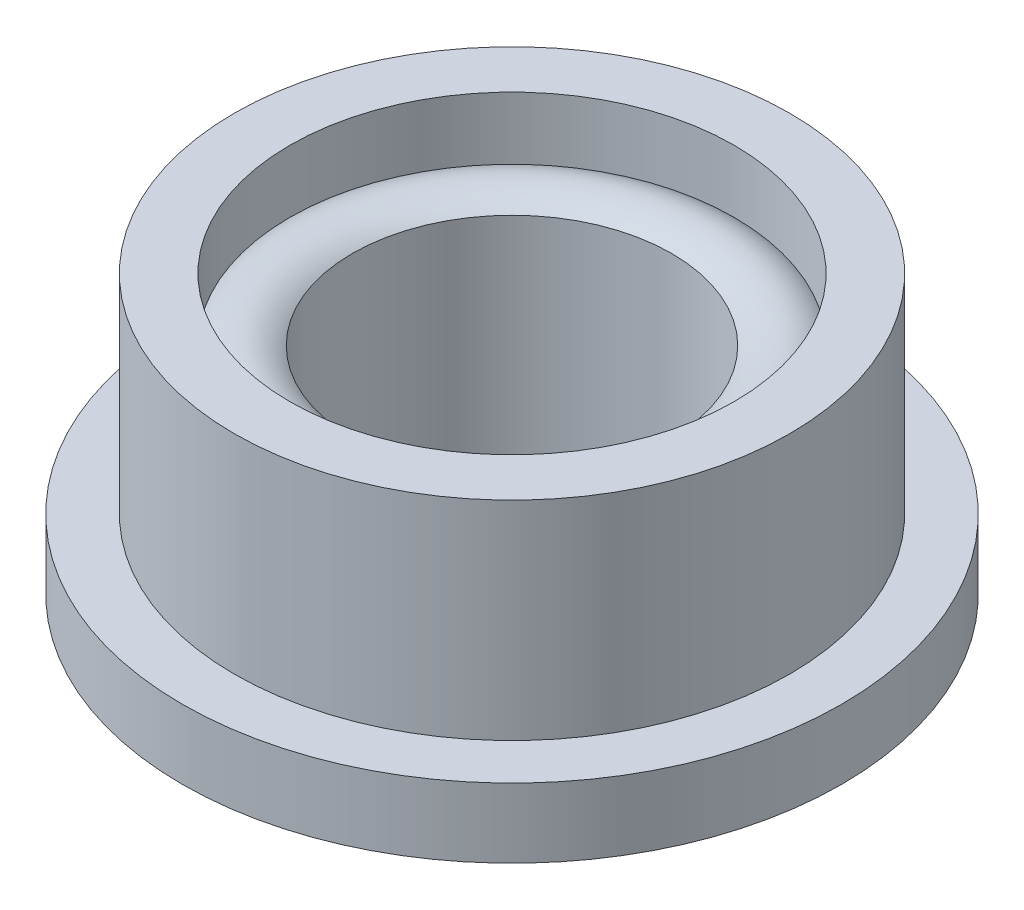
SolidWorks part; units mm, degrees
ref_plane "前视基准面" through (0, 0, 0) normal (0, 0, 1) x (1, 0, 0)
ref_plane "上视基准面" through (0, 0, 0) normal (0, 1, 0) x (1, 0, 0)
ref_plane "右视基准面" through (0, 0, 0) normal (1, 0, 0) x (0, 0, -1)
sketch "Sketch2" plane through (0, 0, 0) normal (0, 1, 0) x (1, 0, 0)
  circle A0 centre (0, 0) radius 4.75
  circle A1 centre (0, 0) radius 1.5
  dimension "D1" = 9.5
  dimension "D2" = 3
extrude "Boss-Extrude1" add sketch "Sketch2" along normal blind 1
sketch "Sketch3" plane through (0, 1, 0) normal (0, 1, 0) x (1, 0, 0)
  circle A0 centre (0, 0) radius 4
  circle A1 centre (0, 0) radius 1.5 construction
  circle A2 centre (0, 0) radius 1.5
  dimension "D1" = 8
extrude "Boss-Extrude2" add sketch "Sketch3" along normal blind 3
sketch "Sketch4" plane through (0, 4, 0) normal (0, 1, 0) x (1, 0, 0)
  circle A0 centre (0, 0) radius 2.3
  circle A1 centre (0, 0) radius 3.2
  dimension "D1" = 4.6
  dimension "D2" = 6.4
extrude "Cut-Extrude1" cut sketch "Sketch4" against normal blind 0.9
sketch "Sketch5" plane through (0, 0, 0) normal (1, 0, 0) x (0, 0, -1)
  line L2 (3.2, 3.1) -> (-3.2, 3.1) construction
  line L3 (2.3, 3.1) -> (-2.3, 3.1) construction
  line L4 (3.2, 3.1) -> (-3.2, 3.1)
  line L5 (2.3, 3.1) -> (-2.3, 3.1)
  arc A0 (-3.2, 3.1) -> (-2.3, 3.1) centre (-2.75, 2.5) cw
  point P5 (-2.75, 3.25)
  dimension "D1" = 0.15
ref_axis "Axis1" through (0, 4, 0) along (0, -1, 0)
revolve "Revolve1" add sketch "Sketch5" angle 360 about axis through (0, 4, 0) along (0, -1, 0) region at (0, 3.1605, 2.75)
sketch "Sketch6" plane through (0, 4, 0) normal (0, 1, 0) x (1, 0, 0)
  circle A0 centre (0, 0) radius 1.5 construction
  circle A1 centre (0, 0) radius 2.3 construction
  circle A2 centre (0, 0) radius 1.5
  circle A3 centre (0, 0) radius 2.3
extrude "Cut-Extrude3" cut sketch "Sketch6" against normal blind 10
